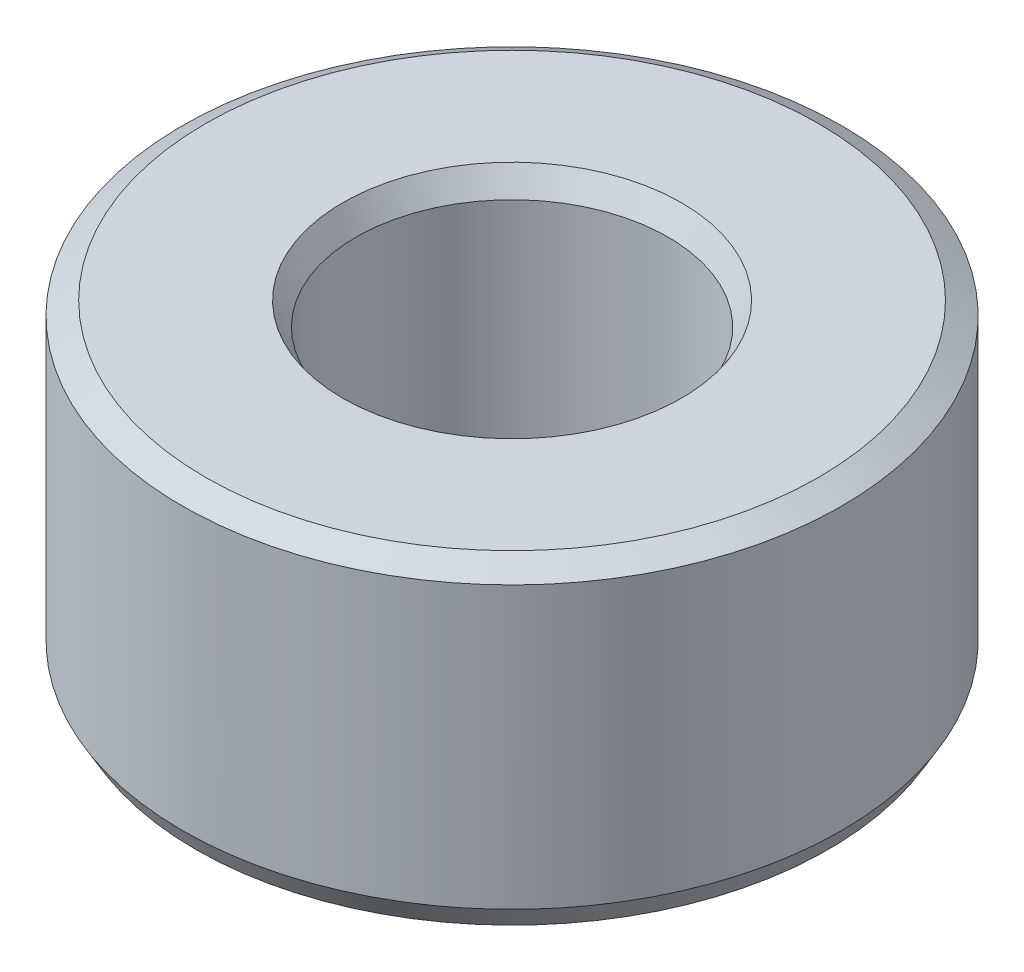
SolidWorks part; units mm, degrees
ref_plane "Front Plane" through (0, 0, 0) normal (0, 0, 1) x (1, 0, 0)
ref_plane "Top Plane" through (0, 0, 0) normal (0, 1, 0) x (1, 0, 0)
ref_plane "Right Plane" through (0, 0, 0) normal (1, 0, 0) x (0, 0, -1)
sketch "Sketch1" plane through (0, 0, 0) normal (0, 1, 0) x (1, 0, 0)
  circle A0 centre (0, 0) radius 17.5
  dimension "SLEEVE_OD" = 35
extrude "Boss-Extrude1" add sketch "Sketch1" along normal blind 16.8538
sketch "Sketch2" plane through (0, 0, 0) normal (0, 1, 0) x (1, 0, 0)
  circle A0 centre (0, 0) radius 8.2859
  dimension "BORE_D" = 16.5718
extrude "Cut-Extrude1" cut sketch "Sketch2" along normal through all
chamfer "Chamfer1" distance 0.7081 angle 60 4 edges at (0, 16.8538, 8.2859) (0, 0, 8.2859) (0, 0, 17.5) (0, 16.8538, 17.5) first distance on face at (0, 16.8538, 8.2859) first distance on face at (0, 0, 8.2859) first distance on face at (0, 16.8538, 17.5)
